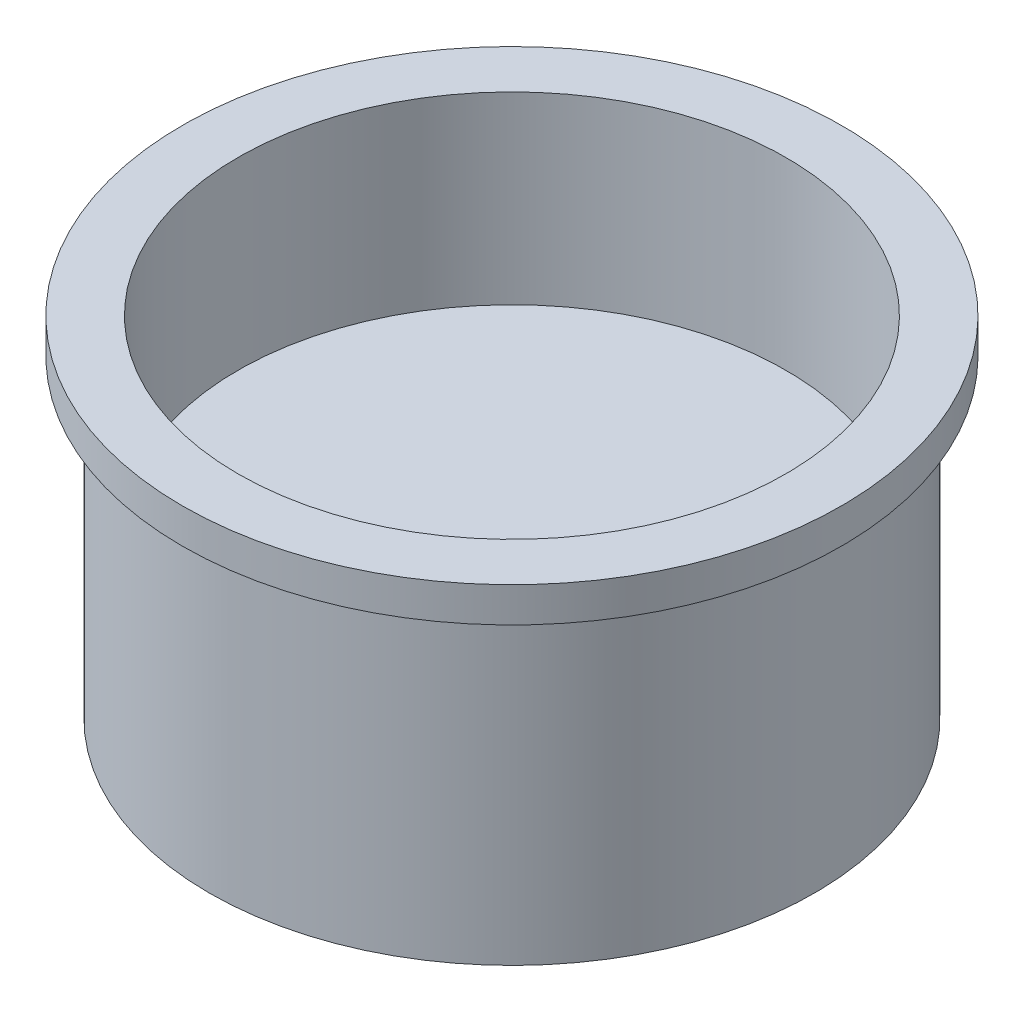
SolidWorks part; units mm, degrees
ref_plane "Front Plane" through (0, 0, 0) normal (0, 0, 1) x (1, 0, 0)
ref_plane "Top Plane" through (0, 0, 0) normal (0, 1, 0) x (1, 0, 0)
ref_plane "Right Plane" through (0, 0, 0) normal (1, 0, 0) x (0, 0, -1)
sketch "Sketch1" plane through (0, 0, 0) normal (0, 1, 0) x (1, 0, 0)
  circle A0 centre (0, 0) radius 12.15
  dimension "D1" = 24.3
extrude "Boss-Extrude1" add sketch "Sketch1" along normal blind 14
sketch "Sketch2" plane through (0, 14, 0) normal (0, 1, 0) x (1, 0, 0)
  circle A0 centre (0, 0) radius 11
  dimension "D1" = 22
extrude "Cut-Extrude1" cut sketch "Sketch2" against normal blind 7.4
sketch "Sketch3" plane through (0, 14, 0) normal (0, 1, 0) x (1, 0, 0)
  circle A0 centre (0, 0) radius 12.15 construction
  circle A1 centre (0, 0) radius 12.15
  circle A2 centre (0, 0) radius 13.23
  dimension "D1" = 1.08
extrude "Boss-Extrude2" add sketch "Sketch3" against normal blind 1.4
